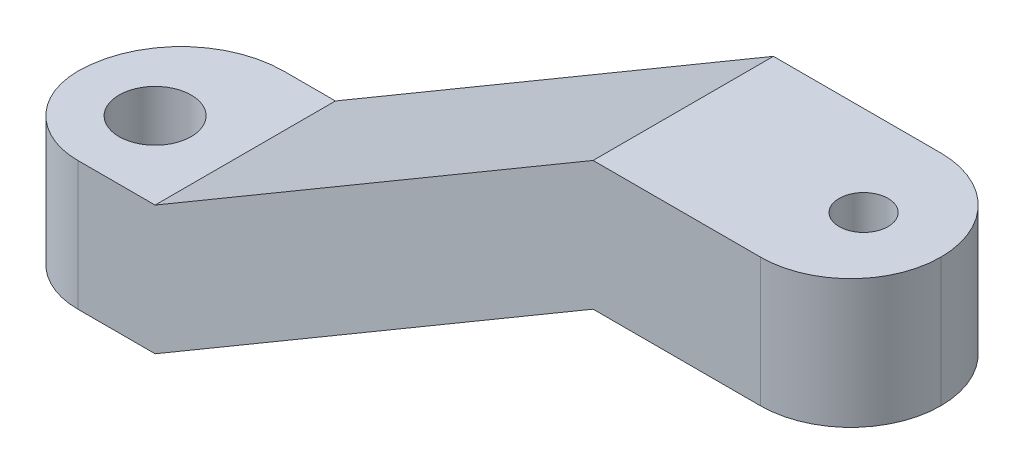
SolidWorks part; units mm, degrees
ref_plane "Plan de face" through (0, 0, 0) normal (0, 0, 1) x (1, 0, 0)
ref_plane "Plan de dessus" through (0, 0, 0) normal (0, 1, 0) x (1, 0, 0)
ref_plane "Plan de droite" through (0, 0, 0) normal (1, 0, 0) x (0, 0, -1)
sketch "Esquisse1" plane through (0, 0, 0) normal (0, 0, 1) x (1, 0, 0)
  line L0 (17, 15) -> (0, 5)
  line L1 (0, 0) -> (-6, 0)
  line L3 (0, 5) -> (-6, 5)
  line L4 (-6, 0) -> (-6, 5)
  line L5 (17, 15) -> (27, 15)
  line L7 (17, 10) -> (27, 10)
  line L8 (27, 15) -> (27, 10)
  line L9 (0, 0) -> (17, 10)
  dimension "D1" = 6
  dimension "D2" = 15
  dimension "D3" = 10
  dimension "D4" = 27
  dimension "D5" = 5
  dimension "D6" = 6
  dimension "D7" = 5
extrude "Boss.-Extru.1" add sketch "Esquisse1" along normal blind 7
sketch "Esquisse3" plane through (0, 5, 0) normal (0, 1, 0) x (1, 0, 0)
  line L0 (0, 0) -> (-6, 0) construction
  line L1 (-6, -7) -> (-6, 0) construction
  circle A0 centre (-3, -4) radius 1.4
  dimension "D3" = 2.8
  dimension "D1" = 4
  dimension "D2" = 3
extrude "Enlèv. mat.-Extru.1" cut sketch "Esquisse3" against normal blind 7
sketch "Esquisse4" plane through (0, 15, 0) normal (0, 1, 0) x (1, 0, 0)
  line L0 (27, 0) -> (17, 0) construction
  line L1 (27, -7) -> (27, 0) construction
  circle A0 centre (24, -3.5) radius 0.95
  dimension "D1" = 1.9
  dimension "D2" = 3.5
  dimension "D3" = 3
extrude "Enlèv. mat.-Extru.2" cut sketch "Esquisse4" against normal blind 7
fillet "Congé1" radius 3.5 2 edges at (27, 12.5, 7) (27, 12.5, 0)
fillet "Congé2" radius 3 1 edges at (-6, 2.5, 7)
fillet "Congé3" radius 4 1 edges at (-6, 2.5, 0)
